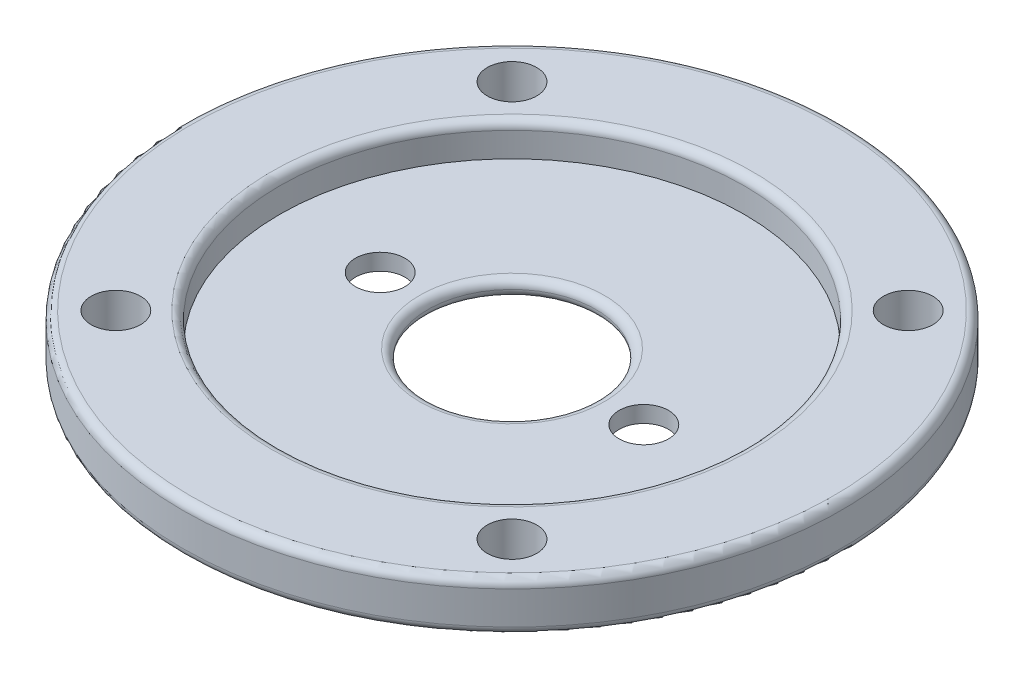
SolidWorks part; units mm, degrees
ref_plane "Front Plane" through (0, 0, 0) normal (0, 0, 1) x (1, 0, 0)
ref_plane "Top Plane" through (0, 0, 0) normal (0, 1, 0) x (1, 0, 0)
ref_plane "Right Plane" through (0, 0, 0) normal (1, 0, 0) x (0, 0, -1)
sketch "Sketch1" plane through (0, 0, 0) normal (0, 0, 1) x (1, 0, 0)
  line L0 (0, 44.0237) -> (0, -24.7716) construction
  line L1 (5.1, 0) -> (20, 0)
  line L2 (5.1, 0) -> (5.1, 1)
  line L3 (5.1, 1) -> (20, 1)
  line L4 (20, 0) -> (20, 1)
  line L5 (14.1, 1) -> (20, 1)
  line L6 (14.1, 1) -> (14.1, 3)
  line L7 (14.1, 3) -> (20, 3)
  line L8 (20, 1) -> (20, 3)
  point P10 (0, 0)
  dimension "D1" = 40
  dimension "D2" = 10.2
  dimension "D3" = 1
  dimension "D4" = 2
  dimension "D5" = 28.2
revolve "Revolve1" add sketch "Sketch1" angle 360 about L0 region at (12.55, 0.5, 0) region at (17.05, 2, 0)
fillet "Fillet1" radius 0.5 5 edges at (0, 0, 5.1) (0, 1, 5.1) (0, 0, 20) (0, 3, 20) (0, 3, 14.1)
sketch "Sketch3" plane through (0, 0, 0) normal (0, 1, 0) x (1, 0, 0)
  circle A0 centre (-8, 0) radius 1.5
  circle A1 centre (8, 0) radius 1.5
  circle A2 centre (0, 0) radius 17 construction
  circle A3 centre (-12.0208, 12.0208) radius 1.5
  circle A4 centre (12.0208, 12.0208) radius 1.5
  circle A5 centre (12.0208, -12.0208) radius 1.5
  circle A6 centre (-12.0208, -12.0208) radius 1.5
  point P7 (0, 0)
  point P11 (0, 0)
  point P20 (0, 0)
  dimension "D1" = 3
  dimension "D4" = 34
  dimension "D5" = 3
  dimension "D2" = 8
  dimension "D3" = 2
  dimension "D6" = 4
extrude "Cut-Extrude1" cut sketch "Sketch3" along normal blind 10
